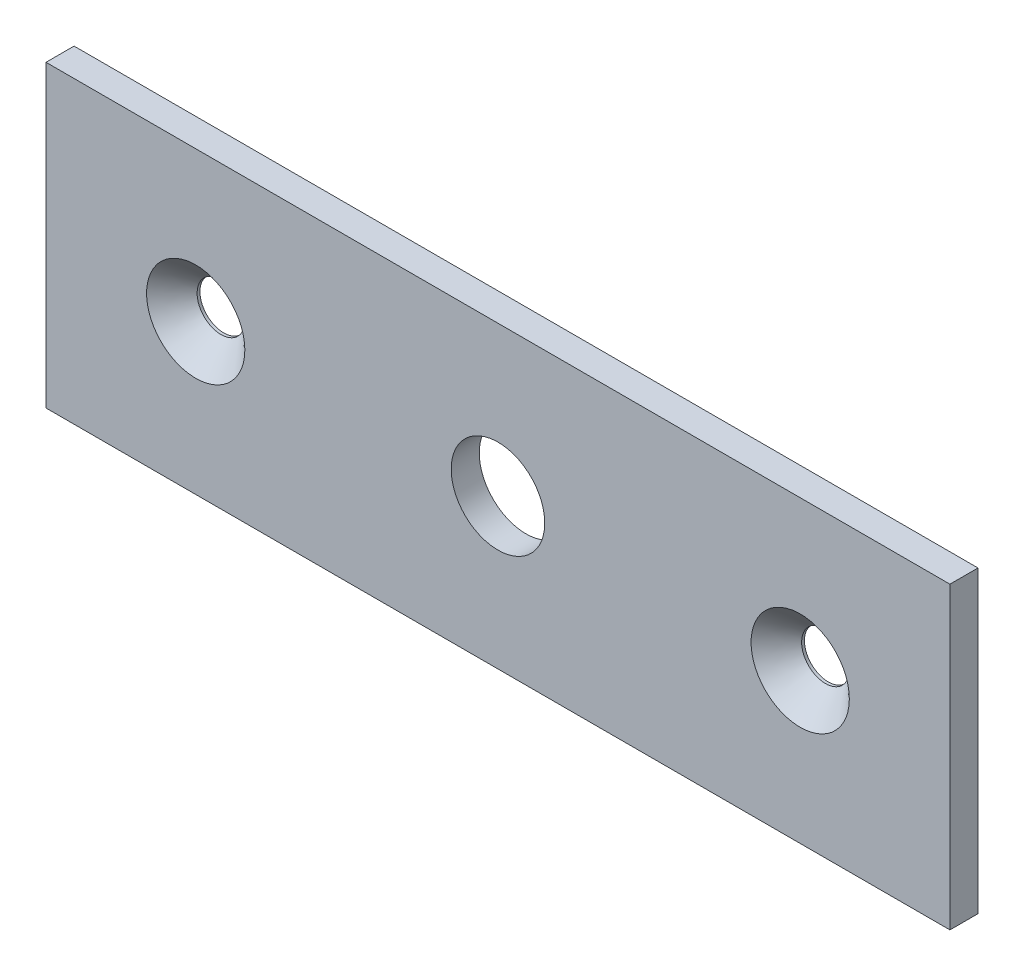
SolidWorks part; units mm, degrees
ref_plane "Plan de face" through (0, 0, 0) normal (0, 0, 1) x (1, 0, 0)
ref_plane "Plan de dessus" through (0, 0, 0) normal (0, 1, 0) x (1, 0, 0)
ref_plane "Plan de droite" through (0, 0, 0) normal (1, 0, 0) x (0, 0, -1)
sketch "Sketch1" plane through (0, 0, 0) normal (0, 0, 1) x (1, 0, 0)
  line L1 (-19.8825, 16.6713) -> (76.7175, 16.6713)
  line L2 (-19.8825, 16.6713) -> (-19.8825, -15.3287)
  line L3 (-19.8825, -15.3287) -> (76.7175, -15.3287)
  line L4 (76.7175, 16.6713) -> (76.7175, -15.3287)
  dimension "D1" = 32
  dimension "D2" = 96.6
extrude "Boss-Extrude1" add sketch "Sketch1" along normal blind 3
sketch "Sketch2" plane through (0, 0, 3) normal (0, 0, 1) x (1, 0, 0)
  line L0 (-19.8825, 16.6713) -> (-19.8825, -15.3287) construction
  line L3 (-19.8825, -15.3287) -> (76.7175, -15.3287) construction
  circle A2 centre (28.4175, 0.6713) radius 5
  point P0 (0, 0)
  point P12 (-19.8825, 0.6713)
  dimension "D7" = 48.3
  dimension "D8" = 16
extrude "Cut-Extrude1" cut sketch "Sketch2" against normal through all
sketch "Esquisse2" plane through (0, 0, 3) normal (0, 0, 1) x (1, 0, 0)
  line L0 (-19.8825, 16.6713) -> (-19.8825, -15.3287) construction
  line L1 (76.7175, -15.3287) -> (76.7175, 16.6713) construction
  line L2 (76.7175, 16.6713) -> (-19.8825, 16.6713) construction
  circle A0 centre (-3.8825, 0.6713) radius 5.25
  circle A1 centre (60.7175, 0.6713) radius 5.25
  dimension "D1" = 10.5
  dimension "D2" = 10.5
  dimension "D3" = 16
  dimension "D4" = 16
  dimension "D5" = 16
  dimension "D6" = 16
hole_wizard "Fraisage pour vis à tête fraisée bombée #51" positions "Esquisse3D1" profile "Esquisse3" countersink size "#5" standard "Ansi Inch" end condition through all
sketch3d "Esquisse3D1"
  point P0 (-3.8825, 0.6713, 3)
  point P3 (60.7175, 0.6713, 3)
sketch "Esquisse3" plane through (-3.8825, 0.6713, 3) normal (1, 0, 0) x (0, -1, 0)
  line L0 (0, 0) -> (0, 3)
  line L1 (0, 3) -> (2.55, 3)
  line L2 (2.55, 3) -> (2.55, 2.7)
  line L3 (2.55, 2.7) -> (5.25, 0)
  line L5 (5.25, 0) -> (0, 0)
  line L6 (-2.55, 2.7) -> (-5.25, 0) construction
  line L11 (0, -6.35) -> (0, 107.95) construction
  dimension "Diamètre du perçage jusqu'au prochain" = 5.1
  dimension "Profondeur du perçage jusqu'au prochain" = 3
  dimension "Diamètre du fraisage entrant" = 10.5
  dimension "Angle du fraisage entrant" = 90
